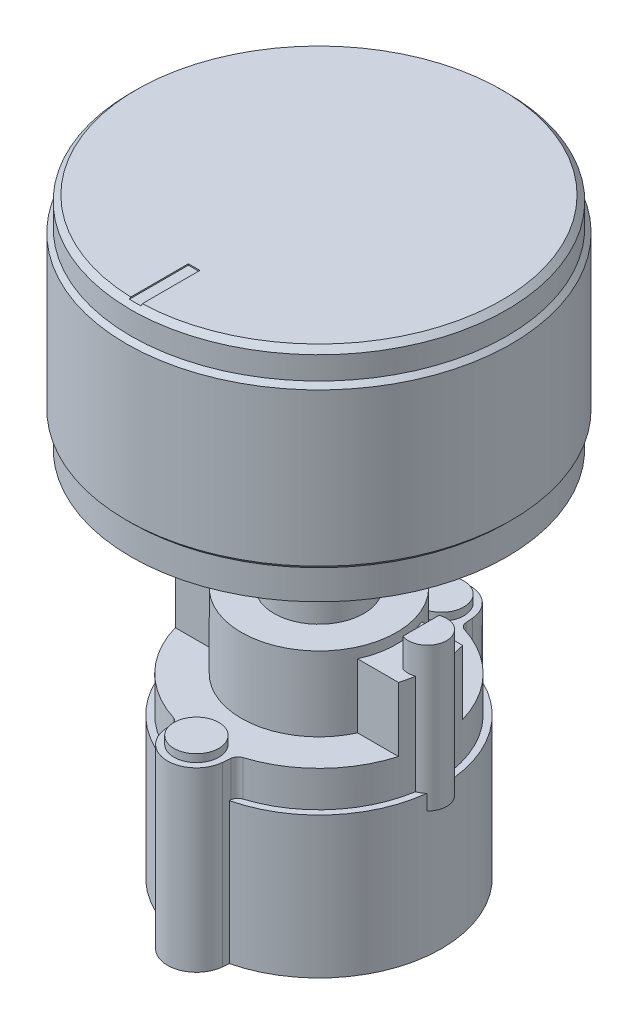
SolidWorks part; units mm, degrees
ref_plane "前基準面" through (0, 0, 0) normal (0, 0, 1) x (1, 0, 0)
ref_plane "上基準面" through (0, 0, 0) normal (0, 1, 0) x (1, 0, 0)
ref_plane "右基準面" through (0, 0, 0) normal (1, 0, 0) x (0, 0, -1)
sketch "草圖2" plane through (0, 0, 0) normal (1, 0, 0) x (0, 0, -1)
  line L0 (0, 22.6125) -> (0, -35.4631) construction
  line L1 (0, 17.1) -> (14.2257, 17.1)
  line L2 (14.2257, 17.1) -> (14.65, 16.6757)
  line L3 (14.65, 16.6757) -> (14.65, 14.9)
  line L4 (14.65, 14.9) -> (15, 14.55)
  line L5 (15, 14.55) -> (15, 2.65)
  line L6 (15, 2.65) -> (14.65, 2.3)
  line L7 (14.65, 2.3) -> (14.65, 0)
  line L8 (14.65, 0) -> (3, 0)
  line L9 (3, 0) -> (3, 15)
  line L10 (3, 15) -> (0, 15)
  line L11 (0, 15) -> (0, 17.1)
  line L13 (2.25, 2.65) -> (2.25, -1.35)
  line L14 (2.25, -1.35) -> (3, -2.1)
  line L15 (3, -2.1) -> (3, -4.1)
  line L16 (3, -4.1) -> (3.5, -4.1)
  line L18 (3.5, -4.1) -> (3.5, -9.4)
  line L19 (3.5, -9.4) -> (6.05, -9.4)
  line L20 (6.05, -9.4) -> (6.05, -15.2)
  line L22 (9.55, -18) -> (9.55, -29)
  line L23 (9.55, -29) -> (0, -29)
  line L24 (0, -29) -> (0, 14.85)
  line L25 (6.05, -15.2) -> (9.05, -15.2)
  line L26 (9.05, -15.2) -> (9.05, -18)
  line L27 (9.05, -18) -> (9.55, -18)
  line L28 (2.25, 2.65) -> (3, 3.4)
  line L29 (3, 3.4) -> (3, 14.1)
  line L30 (3, 14.1) -> (2.25, 14.85)
  line L31 (2.25, 14.85) -> (0, 14.85)
  point P28 (7.55, -15.2)
  dimension "D1" = 30
  dimension "D2" = 2.2
  dimension "D3" = 12.6
  dimension "D4" = 135
  dimension "D5" = 29.3
  dimension "D6" = 17.1
  dimension "D7" = 0.6
  dimension "D8" = 6
  dimension "D9" = 15
  dimension "D10" = 6
  dimension "D11" = 7
  dimension "D12" = 12.1
  dimension "D13" = 19.1
  dimension "D14" = 11
  dimension "D15" = 5.8
  dimension "D16" = 5.3
  dimension "D17" = 18.1
  dimension "D18" = 2.8
  dimension "D19" = 2
  dimension "D20" = 4.5
  dimension "D21" = 135
  dimension "D22" = 6
  dimension "D23" = 12.2
  dimension "D24" = 4
  dimension "D25" = 15.2
revolve "旋轉1" add sketch "草圖2" angle 360 about L0 region at (0, 8.7727, -8.7251)
revolve "旋轉2" add sketch "草圖2<4>" angle 360 about L0 region at (0, -13.2764, -3.5014)
sketch "草圖2<4>" plane through (0, 0, 0) normal (1, 0, 0) x (0, 0, -1) same geometry as "草圖2"
sketch "草圖3" plane through (0, -15.2, 0) normal (0, 1, 0) x (1, 0, 0)
  line L0 (8.6978, 2.5) -> (5.5093, 2.5)
  line L1 (5.5093, 2.5) -> (5.5093, -2.5)
  line L2 (5.5093, -2.5) -> (8.6978, -2.5)
  line L3 (0, 9.968) -> (0, -10.8005) construction
  line L4 (-5.5093, 2.5) -> (-5.5093, -2.5)
  line L5 (-8.6978, 2.5) -> (-5.5093, 2.5)
  line L6 (-5.5093, -2.5) -> (-8.6978, -2.5)
  arc A0 (8.6978, 2.5) -> (8.6978, -2.5) centre (0, 0) cw
  circle A1 centre (0, 0) radius 9.05 construction
  circle A2 centre (0, 0) radius 6.05 construction
  arc A3 (-8.6978, 2.5) -> (-8.6978, -2.5) centre (0, 0) ccw
  dimension "D1" = 5
extrude "填料-伸長1" add sketch "草圖3" along normal blind 5
sketch "草圖4" plane through (0, -10.2, 0) normal (0, 1, 0) x (1, 0, 0)
  line L0 (7.95, 1.4142) -> (7.95, -1.4142)
  arc A0 (7.95, 1.4142) -> (7.95, -1.4142) centre (8.45, 0) cw
  arc A2 (-8.6978, 2.5) -> (-8.6978, -2.5) centre (0, 0) ccw construction
  point P3 (9.95, 0)
  point P4 (0, 0)
  point P11 (-9.05, 0)
  dimension "D2" = 1.5
  dimension "D3" = 19
  dimension "D1" = 2
extrude "填料-伸長2" add sketch "草圖4" against normal blind 11.2 from offset 2.2
sketch "草圖5" plane through (0, -15.2, 0) normal (0, 1, 0) x (1, 0, 0)
  line L0 (-11.9066, 0) -> (12.3951, 0) construction
  line L1 (0, 0) -> (0, 12.2633) construction
  line L2 (-2.2414, 9.7461) -> (-2.2932, 9.1545)
  line L3 (-2.7112, 8.6344) -> (2.7112, 8.6344)
  line L4 (2.2414, 9.7461) -> (2.2932, 9.1545)
  line L5 (2.2414, -9.7461) -> (2.2932, -9.1545)
  line L6 (-2.2414, -9.7461) -> (-2.2932, -9.1545)
  line L7 (-2.7112, -8.6344) -> (2.7112, -8.6344)
  arc A0 (-2.2414, 9.7461) -> (2.2414, 9.7461) centre (0, 9.55) cw
  arc A1 (-2.2932, 9.1545) -> (-2.7112, 8.6344) centre (-2.8909, 9.2068) cw
  arc A2 (-2.2414, -9.7461) -> (2.2414, -9.7461) centre (0, -9.55) ccw
  arc A3 (8.6978, 2.5) -> (-8.6978, 2.5) centre (0, 0) ccw construction
  arc A4 (2.2932, 9.1545) -> (2.7112, 8.6344) centre (2.8909, 9.2068) ccw
  arc A5 (-2.2932, -9.1545) -> (-2.7112, -8.6344) centre (-2.8909, -9.2068) ccw
  arc A6 (2.2932, -9.1545) -> (2.7112, -8.6344) centre (2.8909, -9.2068) cw
  point P5 (0, 8.6344)
  point P17 (0, 11.8)
  dimension "D2" = 2.25
  dimension "D3" = 0.6
  dimension "D1" = 23.6
  dimension "D4" = 5
extrude "填料-伸長3" add sketch "草圖5" against normal up to surface (13.8 mm away) up to face at (0, -29, 9.55)
sketch "草圖6" plane through (0, -15.2, 0) normal (0, 1, 0) x (1, 0, 0)
  line L0 (-11.0051, 0) -> (11.6255, 0) construction
  circle A0 centre (0, 9.55) radius 1.75
  arc A1 (2.2414, 9.7461) -> (-2.2414, 9.7461) centre (0, 9.55) ccw construction
  circle A2 centre (0, -9.55) radius 1.75
  dimension "D1" = 3.5
extrude "填料-伸長4" add sketch "草圖6" along normal blind 0.6
sketch "草圖7" plane through (0, 17.1, 0) normal (0, 1, 0) x (1, 0, 0)
  line L0 (0, -9.7257) -> (0, -14.2257) construction
  line L1 (-0.45, -9.7257) -> (0.45, -9.7257)
  line L2 (-0.45, -9.7257) -> (-0.45, -19.7257)
  line L3 (-0.45, -19.7257) -> (0.45, -19.7257)
  line L4 (0.45, -9.7257) -> (0.45, -19.7257)
  circle A0 centre (0, 0) radius 14.2257 construction
  point P4 (0, -9.7257)
  dimension "D1" = 0.9
  dimension "D2" = 10
  dimension "D3" = 4.5
extrude "除料-伸長1" cut sketch "草圖7" against normal blind 0.1
